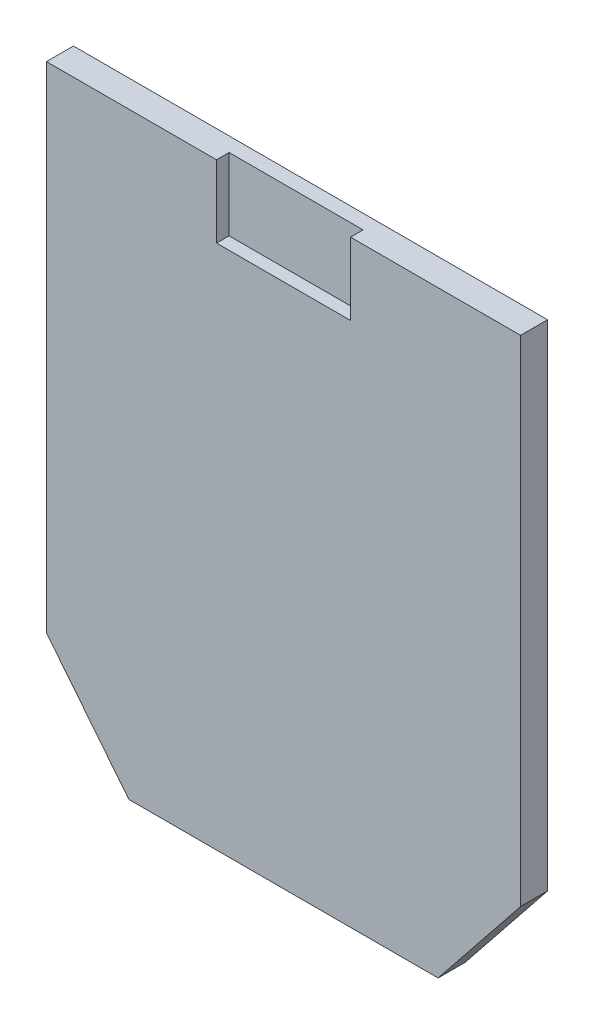
SolidWorks part; units mm, degrees
ref_plane "Front Plane" through (0, 0, 0) normal (0, 0, 1) x (1, 0, 0)
ref_plane "Top Plane" through (0, 0, 0) normal (0, 1, 0) x (1, 0, 0)
ref_plane "Right Plane" through (0, 0, 0) normal (1, 0, 0) x (0, 0, -1)
sketch "Sketch1" plane through (0, 0, 0) normal (0, 0, 1) x (1, 0, 0)
  line L0 (0, 0) -> (0, -170) construction
  line L2 (115, -120) -> (115, 120)
  line L3 (115, 120) -> (-115, 120)
  line L4 (-115, -120) -> (-115, 120)
  line L5 (115, -120) -> (-115, 120) construction
  line L6 (115, 120) -> (-115, -120) construction
  line L7 (75, -170) -> (-75, -170)
  line L11 (-115, -120) -> (115, -120) construction
  line L14 (115, -120) -> (75, -170)
  line L15 (-115, -120) -> (-75, -170)
  point P0 (0, 0)
  dimension "D1" = 240
  dimension "D2" = 230
  dimension "D3" = 40
  dimension "D4" = 50
extrude "Boss-Extrude1" add sketch "Sketch1" along normal blind 13.1
fillet "Fillet1" radius 5 6 edges at (-115, 120, 6.55) (115, 120, 6.55) (75, -170, 6.55) (-75, -170, 6.55) (-115, -120, 6.55) (115, -120, 6.55)
sketch "Sketch2" plane through (0, 0, 13.1) normal (0, 0, 1) x (1, 0, 0)
  line L0 (110, 120) -> (-110, 120) construction
  line L1 (-32.5, 120) -> (32.5, 120)
  line L2 (-32.5, 120) -> (-32.5, 85)
  line L3 (-32.5, 85) -> (32.5, 85)
  line L4 (32.5, 120) -> (32.5, 85)
  line L5 (-32.5, 120) -> (32.5, 85) construction
  line L6 (-32.5, 85) -> (32.5, 120) construction
  line L7 (0, 102.5) -> (0, 0) construction
  point P0 (0, 102.5)
  dimension "D1" = 65
  dimension "D2" = 35
extrude "Cut-Extrude1" cut sketch "Sketch2" against normal through all
fillet "Fillet2" [suppressed] radius 5
sketch "Sketch3" plane through (0, 0, 13.1) normal (0, 0, 1) x (1, 0, 0)
  line L0 (-32.5, 120) -> (-110, 120) construction
  line L1 (-52.1786, 120) -> (57.2952, 120)
  line L2 (-52.1786, 120) -> (-52.1786, 71.0554)
  line L3 (-52.1786, 71.0554) -> (57.2952, 71.0554)
  line L4 (57.2952, 120) -> (57.2952, 71.0554)
extrude "Boss-Extrude2" add sketch "Sketch3" against normal blind 7
sketch "Sketch4" plane through (0, 0, 0) normal (0, 0, -1) x (-1, 0, 0)
  point P0 (53.5, -55.89)
  point P1 (106.5, -55.89)
  point P3 (106.5, -95.89)
  point P5 (53.5, -95.89)
  point P7 (-53.5, -55.89)
  point P9 (-53.5, -95.89)
  point P11 (-106.5, -95.89)
  point P13 (-106.5, -55.89)
  point P15 (-106.5, 101.37)
  point P17 (-53.5, 101.37)
  point P19 (-53.5, 61.37)
  point P21 (-106.5, 61.37)
  point P23 (53.5, 101.37)
  point P25 (53.5, 61.37)
  point P27 (106.5, 101.37)
  point P29 (106.5, 61.37)
  point P31 (62.5, -110)
  point P33 (62.5, -150)
  point P35 (-62.5, -110)
  point P37 (-62.5, -150)
  point P39 (-17.5, 64.95)
  point P41 (-17.5, 40.95)
  point P43 (17.5, 40.95)
  point P45 (17.5, 64.95)
sketch "Sketch5" plane through (0, 0, 13.1) normal (0, 0, 1) x (1, 0, 0)
  circle A0 centre (106.5, 101.37) radius 3.3
  circle A1 centre (53.5, 101.37) radius 3.3
  circle A2 centre (53.5, 61.37) radius 3.3
  circle A3 centre (106.5, 61.37) radius 3.3
  circle A4 centre (-53.5, 101.37) radius 3.3
  circle A5 centre (-106.5, 101.37) radius 3.3
  circle A6 centre (-106.5, 61.37) radius 3.3
  circle A7 centre (-53.5, 61.37) radius 3.3
  circle A8 centre (-106.5, -55.89) radius 3.3
  circle A9 centre (-53.5, -55.89) radius 3.3
  circle A10 centre (-53.5, -95.89) radius 3.3
  circle A11 centre (-106.5, -95.89) radius 3.3
  circle A12 centre (53.5, -55.89) radius 3.3
  circle A13 centre (106.5, -55.89) radius 3.3
  circle A14 centre (106.5, -95.89) radius 3.3
  circle A15 centre (53.5, -95.89) radius 3.3
  dimension "D1" = 6.6
extrude "Cut-Extrude2" [suppressed] cut sketch "Sketch5" against normal through all
sketch "Sketch6" plane through (0, 0, 13.1) normal (0, 0, 1) x (1, 0, 0)
  circle A0 centre (17.5, 64.95) radius 2.5
  circle A1 centre (17.5, 40.95) radius 2.5
  circle A2 centre (-17.5, 64.95) radius 2.5
  circle A3 centre (-17.5, 40.95) radius 2.5
  dimension "D1" = 5
extrude "Cut-Extrude3" [suppressed] cut sketch "Sketch6" against normal through all
sketch "Sketch8" plane through (0, 0, 13.1) normal (0, 0, 1) x (1, 0, 0)
  circle A0 centre (62.5, -110) radius 2.5
  circle A1 centre (62.5, -150) radius 2.5
  circle A2 centre (-62.5, -110) radius 2.5
  circle A3 centre (-62.5, -150) radius 2.5
  dimension "D1" = 5
extrude "Cut-Extrude4" [suppressed] cut sketch "Sketch8" against normal through all
sketch "Sketch9" [suppressed] plane through (0, 0, 13.1) normal (0, 0, 1) x (1, 0, 0)
  circle A0 centre (53.5, -95.89) radius 5.5
  circle A1 centre (-53.5, -95.89) radius 5.5
  dimension "D1" = 11
extrude "Cut-Extrude5" [suppressed] cut sketch "Sketch9" against normal blind 6
move or copy body "Body-Move/Copy1" bodies to move or copy 103 copy no rotation origin (0, 0, 6) rotation axis (0, 1, 0) rotation angle 180
sketch3d "3DSketch1"
  line L0 (-115, 115, -1.1) -> (-115, 120, -1.1) construction
  line L1 (-115, 120, -1.1) -> (-110, 120, -1.1) construction
  line L2 (-115, 120, -1.1) -> (-115, 120, 12) construction
sketch "Sketch10" plane through (0, 0, 12) normal (0, 0, 1) x (1, 0, 0)
  line L0 (37.5, -17.5) -> (37.5, -77.5) construction
  line L1 (115, 115) -> (115, -118.2461) construction
  line L3 (37.5, -47.5) -> (115, -47.5) construction
  line L4 (72.5969, -170) -> (-72.5969, -170) construction
  circle A0 centre (37.5, -17.5) radius 2.65
  circle A1 centre (37.5, -77.5) radius 2.65
  dimension "D2" = 5.3
  dimension "D1" = 77.5
  dimension "D3" = 60
  dimension "D4" = 122.5
extrude "Cut-Extrude6" [suppressed] cut sketch "Sketch10" against normal mid plane 40
other "DeleteFace1" face at (113.0178, 118.0178, 5.45) face at (114.5852, -119.8545, 5.45) face at (74.6559, -169.2841, 5.45) face at (-74.6559, -169.2841, 5.45) face at (-114.5852, -119.8545, 5.45) face at (-113.0178, 118.0178, 5.45) and patch yes
equation "\"M4 Clearence\"= 4.5mm"
equation "\"M6 Threaded\"= 5mm"
equation "\"M6 Clearence\"= 6.6mm"
equation "\"D1@Sketch6\"=\"M6 Threaded\""
equation "\"D1@Sketch5\"=\"M6 Clearence\""
equation "\"D1@Sketch8\"=\"M6 Threaded\""
equation "\"M5 Clearence\"= 5.5mm"
